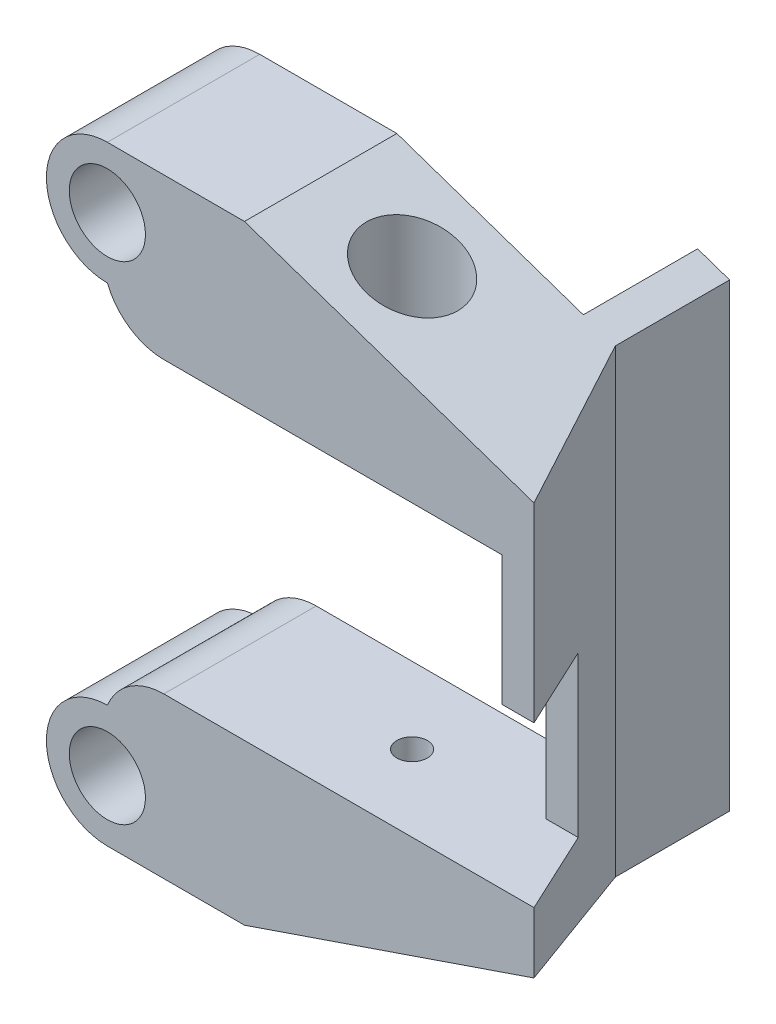
SolidWorks part; units mm, degrees
ref_plane "Alzado" through (0, 0, 0) normal (0, 0, 1) x (1, 0, 0)
ref_plane "Planta" through (0, 0, 0) normal (0, 1, 0) x (1, 0, 0)
ref_plane "Vista lateral" through (0, 0, 0) normal (1, 0, 0) x (0, 0, -1)
sketch "Croquis1" plane through (0, 0, 0) normal (0, 0, 1) x (1, 0, 0)
  line L5 (-103.2316, 22.7007) -> (-131.2316, 22.7007)
  line L6 (-131.2316, 22.7007) -> (-131.2316, 20.2007)
  line L7 (-103.2316, 22.7007) -> (-103.2316, 18.7007)
  line L8 (-103.2316, 18.7007) -> (-125.2316, 18.7007)
  line L9 (-125.2316, 18.7007) -> (-125.2316, 12.2007)
  line L10 (-125.2316, 12.2007) -> (-131.2316, 12.2007)
  circle A0 centre (-131.2316, 16.2007) radius 2.5
  arc A2 (-131.2316, 20.2007) -> (-131.2316, 12.2007) centre (-131.2316, 16.2007) ccw
  dimension "D1" = 4
  dimension "D2" = 5
  dimension "D3" = 6
  dimension "D9" = 1.5
  dimension "D7" = 4
  dimension "D4" = 6.5
  dimension "D5" = 28
  dimension "D6" = 6.5
  dimension "D8" = 2.5
extrude "Saliente-Extruir1" add sketch "Croquis1" along normal blind 10
sketch "Croquis2" plane through (0, 18.7007, 0) normal (0, -1, 0) x (1, 0, 0)
  line L1 (-103.2316, -0.4651) -> (-103.2316, 10)
  line L2 (-103.2316, 10) -> (-108.1116, -0.4651)
  line L4 (-108.1116, -0.4651) -> (-103.2316, -0.4651)
  line L6 (-103.2316, 10) -> (-103.2316, 0) construction
  circle A0 centre (-116.2316, 5) radius 1
  dimension "D1" = 13
  dimension "D2" = 25
  dimension "D3" = 0
extrude "Cortar-Extruir1" cut sketch "Croquis2" against normal up to vertex (4 mm away) up to point (-103.2316, 22.7007, 10)
sketch "Croquis3" plane through (0, 18.7007, 0) normal (0, -1, 0) x (1, 0, 0)
  line L0 (-103.2316, 10) -> (-105.3316, 10)
  line L1 (-105.3316, 10) -> (-109.9947, 0)
  line L2 (-109.9947, 0) -> (-107.8947, 0)
  line L3 (-103.2316, 10) -> (-107.8947, 0)
  dimension "D1" = 2.1
  dimension "D2" = 2.1
extrude "Saliente-Extruir2" add sketch "Croquis3" against normal blind 13.5
sketch "Croquis4" plane through (0, 18.7007, 0) normal (0, -1, 0) x (1, 0, 0)
  circle A0 centre (-116.2316, 5) radius 3
extrude "Cortar-Extruir2" cut sketch "Croquis4" against normal blind 1
sketch "Croquis6" plane through (0, 18.7007, 0) normal (0, -1, 0) x (1, 0, 0)
  line L0 (-125.2316, 10) -> (-103.2316, 10)
  line L1 (-103.2316, 10) -> (-107.8947, 0)
  line L2 (-107.8947, 0) -> (-125.2316, 0)
  line L3 (-125.2316, 0) -> (-125.2316, 10)
  circle A0 centre (-116.2316, 5) radius 3
extrude "Saliente-Extruir3" add sketch "Croquis6" along normal up to vertex (6.5 mm away) up to point (-125.2316, 12.2007, 10)
sketch "Croquis7" plane through (0, 0, 10) normal (0, 0, 1) x (1, 0, 0)
  line L1 (-103.2316, 12.2007) -> (-103.2316, 32.2007) construction
  line L4 (-103.2316, 18.7007) -> (-103.2316, 12.2007)
  line L5 (-103.2316, 12.2007) -> (-122.2316, 12.2007)
  line L6 (-131.2316, 12.2007) -> (-103.2316, 12.2007) construction
  line L7 (-122.2316, 12.2007) -> (-103.2316, 18.7007)
  dimension "D1" = 19
  dimension "D2" = 6.5
extrude "Cortar-Extruir4" cut sketch "Croquis7" against normal blind 10
sketch "Croquis5" plane through (0, 0, 10) normal (0, 0, 1) x (1, 0, 0)
  line L0 (-103.2316, 18.7007) -> (-103.2316, 32.2007) construction
  line L1 (-105.3316, 22.7007) -> (-103.2316, 22.7007)
  line L2 (-105.3316, 22.7007) -> (-105.3316, 33.2007)
  line L3 (-105.3316, 33.2007) -> (-103.2316, 33.2007)
  line L4 (-103.2316, 22.7007) -> (-103.2316, 33.2007)
  dimension "D1" = 10.5
sketch "Croquis8" plane through (0, 0, 0) normal (0, 0, -1) x (-1, 0, 0)
  line L0 (107.8947, 17.1054) -> (107.8947, 32.2007)
  line L1 (107.8947, 32.2007) -> (109.9947, 32.2007)
  line L2 (109.9947, 32.2007) -> (109.9947, 22.7007)
  line L3 (109.9947, 22.7007) -> (109.9947, 16.387)
  line L4 (107.8947, 17.1054) -> (122.2316, 12.2007) construction
  line L5 (109.9947, 16.387) -> (107.8947, 17.1054)
extrude "Saliente-Extruir4" add sketch "Croquis8" along normal blind 7.5
mirror "Simetría1" about plane through (0, 32.2007, 0) normal (0, -1, 0) of bodies 110
extrude "Cortar-Extruir5" cut sketch "Croquis5" along direction (-0.4226, 0, -0.9063) on the side against the normal blind 6
fillet "Redondeo1" radius 4 2 edges at (-131.2316, 41.7007, 5) (-131.2316, 22.7007, 5)
sketch "Croquis9" plane through (0, 12.2007, 0) normal (0, -1, 0) x (1, 0, 0)
  text T0 "25º"
extrude "Cortar-Extruir6" cut sketch "Croquis9" against normal blind 1
